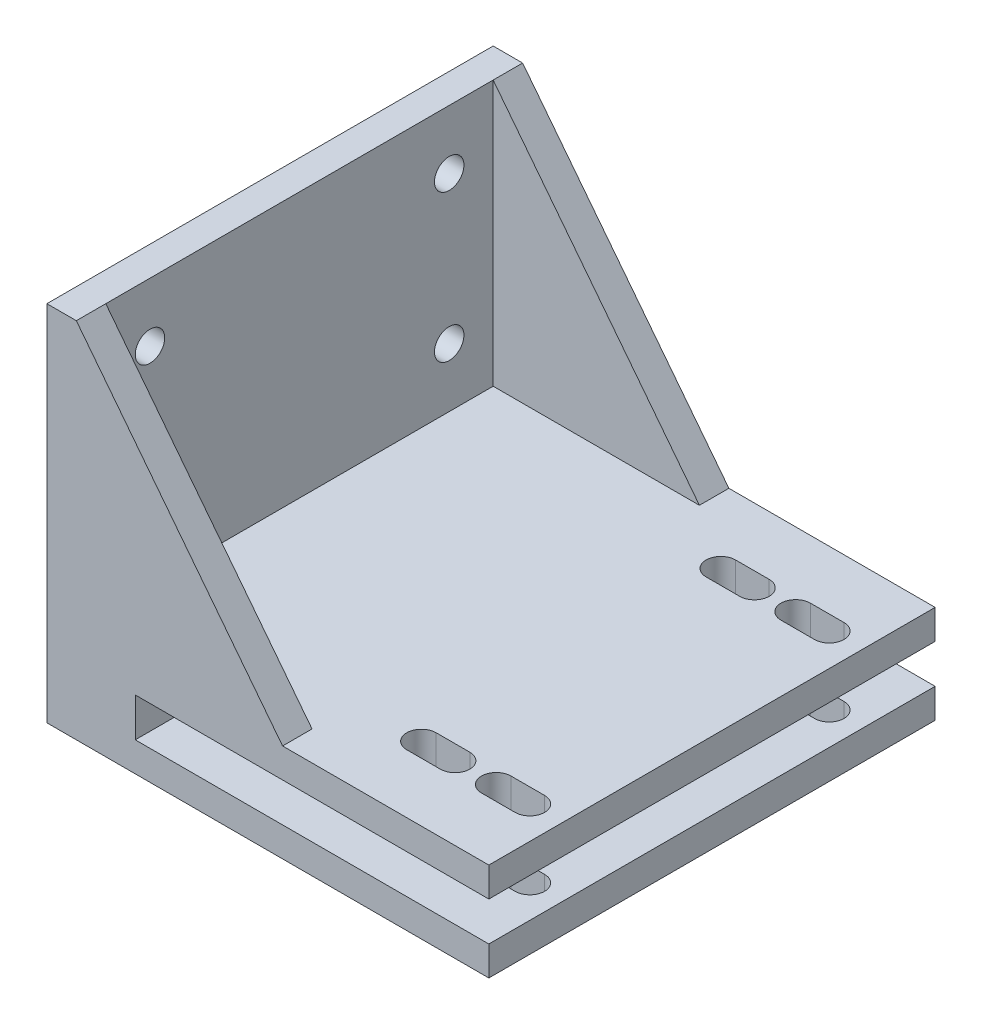
SolidWorks part; units mm, degrees
ref_plane "Front Plane" through (0, 0, 0) normal (0, 0, 1) x (1, 0, 0)
ref_plane "Top Plane" through (0, 0, 0) normal (0, 1, 0) x (1, 0, 0)
ref_plane "Right Plane" through (0, 0, 0) normal (1, 0, 0) x (0, 0, -1)
sketch "Sketch1" plane through (0, 0, 0) normal (0, 1, 0) x (1, 0, 0)
  line L1 (0, 0) -> (75, 0)
  line L2 (0, 0) -> (0, 15)
  line L3 (0, 15) -> (75, 15)
  line L4 (75, 0) -> (75, 15)
  dimension "D1" = 15
  dimension "D2" = 75
extrude "Boss-Extrude1" add sketch "Sketch1" along normal blind 5
sketch "Sketch2" plane through (0, 5, 0) normal (0, 1, 0) x (1, 0, 0)
  line L0 (0, 15) -> (5, 15)
  line L1 (75, 15) -> (0, 15) construction
  line L2 (0, 0) -> (5, 0)
  line L3 (0, 0) -> (75, 0) construction
  line L4 (5, 15) -> (5, 0)
  line L5 (0, 15) -> (0, 0)
extrude "Boss-Extrude2" add sketch "Sketch2" along normal blind 45
sketch "Sketch3" plane through (0, 0, 0) normal (0, -1, 0) x (-1, 0, 0)
  line L0 (0, 7.5) -> (-75, 7.5)
  line L1 (0, 15) -> (0, 0) construction
  line L2 (-75, 0) -> (-75, 15) construction
sketch "Sketch4" plane through (0, 0, 0) normal (-1, 0, 0) x (0, 0, 1)
  line L0 (-7.5, 0) -> (-7.5, 50)
  line L2 (-15, 0) -> (0, 0) construction
  line L3 (-7.5, 0) -> (-7.5, 15)
  line L4 (-7.5, 50) -> (-7.5, 40)
hole_wizard "Ø5.0mm Dowel Hole1" positions "Sketch5" profile "Sketch6" hole size "Ø5.0" standard "ANSI Metric" end condition up to next
sketch "Sketch5" plane through (0, 0, 0) normal (-1, 0, 0) x (0, 0, 1)
  point P0 (-7.5, 40)
  point P3 (-7.5, 15)
  point P6 (0, 0)
  point P7 (-7.5, 40)
sketch "Sketch6" plane through (0, 40, -7.5) normal (0, 1, 0) x (0, 0, 1)
  line L0 (0, 0) -> (0, 5)
  line L1 (0, 5) -> (2.5, 5)
  line L2 (2.5, 5) -> (2.5, 0)
  line L5 (2.5, 0) -> (0, 0)
  line L11 (0, -6.35) -> (0, 107.95) construction
  dimension "Thru Hole Dia." = 5
  dimension "Thru Hole Depth" = 5
hole_wizard "Ø6.0mm Dowel Slot1" positions "Sketch9" profile "Sketch8" size "Ø5.0" standard "ANSI Metric" slot yes end condition up to next
sketch "Sketch9" plane through (0, 0, 0) normal (0, -1, 0) x (-1, 0, 0)
  line L1 (-48.5943, 7.4749) -> (-59.2943, 7.4749) construction
  point P5 (-53.9443, 7.4749)
  point P10 (-66.6443, 7.465)
  dimension "D2" = 10.7
sketch "Sketch8" plane through (53.9443, 0, -7.4749) normal (1, 0, 0) x (0, 0, -1)
  line L0 (0, 0) -> (0, 5)
  line L1 (0, 5) -> (2.5, 5)
  line L2 (2.5, 5) -> (2.5, 0)
  line L5 (2.5, 0) -> (0, 0)
  line L11 (0, -6.35) -> (0, 107.95) construction
  dimension "Thru Hole Dia." = 5
  dimension "Thru Hole Depth" = 5
sketch "Sketch10" plane through (0, 0, 0) normal (0, 0, 1) x (1, 0, 0)
  line L0 (5, 50) -> (40, 5)
  line L1 (5, 5) -> (75, 5) construction
  line L2 (40, 5) -> (75, 5)
  line L3 (75, 5) -> (75, 0)
  line L4 (75, 0) -> (0, 0)
  line L5 (0, 0) -> (0, 50)
  line L6 (0, 50) -> (5, 50)
extrude "Boss-Extrude3" add sketch "Sketch10" along normal blind 5
sketch "Sketch21" plane through (0, 0, -15) normal (0, 0, -1) x (-1, 0, 0)
  line L0 (-75, 5) -> (-5, 5)
  line L1 (-5, 5) -> (-5, 50)
  line L2 (-5, 50) -> (0, 50)
  line L3 (0, 50) -> (0, 0)
  line L4 (0, 0) -> (-75, 0)
  line L5 (-75, 0) -> (-75, 5)
extrude "Boss-Extrude7" add sketch "Sketch21" along normal blind 46.8
sketch "Sketch22" plane through (0, 0, -61.8) normal (0, 0, -1) x (-1, 0, 0)
  line L0 (-75, 5) -> (-40, 5)
  line L1 (-5, 5) -> (-75, 5) construction
  line L3 (-5, 50) -> (0, 50)
  line L4 (0, 50) -> (0, 0)
  line L5 (0, 0) -> (-75, 0)
  line L6 (-75, 0) -> (-75, 5)
  line L7 (-40, 5) -> (-5, 5)
  line L9 (-5, 50) -> (-5, 5)
sketch "Sketch23" plane through (0, 0, 0) normal (0, -1, 0) x (-1, 0, 0)
  line L0 (-53.9443, 4.9749) -> (-53.9443, 9.9749)
  line L1 (-51.0943, 4.9749) -> (-56.7943, 4.9749) construction
  line L2 (-51.0943, 9.9749) -> (-56.7943, 9.9749) construction
  line L3 (-53.9443, 9.9749) -> (-53.9443, 7.4749)
  line L4 (-53.9443, 7.4749) -> (-59.2943, 7.4749)
  line L5 (-66.6443, 9.965) -> (-66.6443, 4.965)
  line L6 (-63.7943, 9.965) -> (-69.4943, 9.965) construction
  line L7 (-63.7943, 4.965) -> (-69.4943, 4.965) construction
  line L8 (-66.6443, 4.965) -> (-66.6443, 7.465)
  line L9 (-66.6443, 7.465) -> (-61.2943, 7.465)
  arc A0 (-56.7943, 9.9749) -> (-56.7943, 4.9749) centre (-56.7943, 7.4749) ccw construction
  arc A1 (-63.7943, 4.965) -> (-63.7943, 9.965) centre (-63.7943, 7.465) ccw construction
sketch "Sketch25" plane through (0, 0, 0) normal (0, -1, 0) x (1, 0, 0)
  line L0 (66.6443, -7.465) -> (66.6443, -58.265)
  line L1 (66.6443, -58.265) -> (66.6443, -70.735)
extrude "Boss-Extrude11" add sketch "Sketch22" along normal up to vertex (8.935 mm away) up to point (66.6443, 0, -70.735)
sketch "Sketch29" plane through (0, 0, 0) normal (0, -1, 0) x (1, 0, 0)
  line L0 (0, -70.735) -> (15, -70.735)
  line L1 (75, -70.735) -> (0, -70.735) construction
  line L2 (15, -70.735) -> (15, 5)
  line L3 (0, 5) -> (75, 5) construction
  line L4 (15, 5) -> (0, 5)
  line L5 (0, 5) -> (0, -70.735)
extrude "Boss-Extrude12" add sketch "Sketch29" along normal blind 11.6
sketch "Sketch30" plane through (15, 0, 0) normal (1, 0, 0) x (0, 0, -1)
  line L0 (70.735, -11.6) -> (70.735, -6.6)
  line L1 (70.735, -11.6) -> (70.735, 0) construction
  line L2 (70.735, -6.6) -> (-5, -6.6)
  line L3 (-5, -11.6) -> (-5, 0) construction
  line L4 (-5, -6.6) -> (-5, -11.6)
  line L5 (-5, -11.6) -> (70.735, -11.6)
extrude "Boss-Extrude13" add sketch "Sketch30" along normal up to surface (60 mm away) up to face at (75, 2.5, -32.8675)
sketch "Sketch31" plane through (0, 0, -70.735) normal (0, 0, -1) x (-1, 0, 0)
  line L0 (-5, 50) -> (-40, 5)
  line L1 (-5, 5) -> (-75, 5) construction
  line L2 (-40, 5) -> (-5, 5)
  line L3 (-5, 5) -> (-5, 50)
extrude "Boss-Extrude14" add sketch "Sketch31" against normal blind 5
hole_wizard "Ø5.0mm Dowel Slot2" positions "Sketch32" profile "Sketch33" size "Ø5.0" standard "ANSI Metric" slot yes end condition through all
sketch "Sketch32" plane through (0, 5, 0) normal (0, 1, 0) x (1, 0, 0)
  line L0 (61.2943, 58.2749) -> (71.9943, 58.2749) construction
  point P0 (66.6443, 58.2749)
  point P5 (53.9443, 58.2749)
  point P9 (0, 0)
  point P10 (0, 0)
  dimension "D1" = 10.7
sketch "Sketch33" plane through (66.6443, 5, -58.2749) normal (1, 0, 0) x (0, 0, 1)
  line L0 (0, 0) -> (0, 16.6)
  line L1 (0, 16.6) -> (2.5, 16.6)
  line L2 (2.5, 16.6) -> (2.5, 0)
  line L5 (2.5, 0) -> (0, 0)
  line L11 (0, -6.35) -> (0, 107.95) construction
  dimension "Thru Hole Dia." = 5
  dimension "Thru Hole Depth" = 16.6
hole_wizard "Ø5.0mm Dowel Slot3" positions "Sketch36" profile "Sketch35" size "Ø5.0" standard "ANSI Metric" slot yes end condition through all
sketch "Sketch36" plane through (0, 0, 0) normal (0, -1, 0) x (-1, 0, 0)
  line L0 (-61.2943, 7.465) -> (-71.9943, 7.465) construction
  point P0 (-66.6443, 7.465)
  point P5 (-53.9443, 7.4749)
  dimension "D1" = 10.7
sketch "Sketch35" plane through (66.6443, 0, -7.465) normal (1, 0, 0) x (0, 0, 1)
  line L0 (0, 0) -> (0, 11.6)
  line L1 (0, 11.6) -> (2.5, 11.6)
  line L2 (2.5, 11.6) -> (2.5, 0)
  line L5 (2.5, 0) -> (0, 0)
  line L11 (0, -6.35) -> (0, 107.95) construction
  dimension "Thru Hole Dia." = 5
  dimension "Thru Hole Depth" = 11.6
sketch "Sketch38" plane through (0, 0, 0) normal (0, -1, 0) x (-1, 0, 0)
  line L0 (-15, 32.8675) -> (-75, 32.8675)
  line L1 (-15, 70.735) -> (-15, -5) construction
  line L2 (-75, -5) -> (-75, 70.735) construction
sketch "Sketch39" plane through (0, 5, 0) normal (0, 1, 0) x (1, 0, 0)
  line L0 (48.5943, 58.2749) -> (5, 58.2749)
  line L1 (5, 0) -> (5, 65.735) construction
  arc A0 (51.0943, 60.7749) -> (51.0943, 55.7749) centre (51.0943, 58.2749) ccw construction
sketch "Sketch40" plane through (5, 0, 0) normal (1, 0, 0) x (0, 0, -1)
  line L0 (58.2749, 5) -> (58.2749, 50)
  line L1 (0, 50) -> (65.735, 50) construction
  line L2 (58.2749, 50) -> (58.2749, 40)
  line L3 (58.2749, 5) -> (58.2749, 15)
hole_wizard "Ø5.0mm Dowel Hole2" positions "Sketch41" profile "Sketch42" hole size "Ø5.0" standard "ANSI Metric" end condition up to next
sketch "Sketch41" plane through (5, 0, 0) normal (1, 0, 0) x (0, 0, -1)
  point P0 (58.2749, 40)
  point P3 (58.2749, 15)
sketch "Sketch42" plane through (5, 40, -58.2749) normal (0, 1, 0) x (0, 0, -1)
  line L0 (0, 0) -> (0, 5)
  line L1 (0, 5) -> (2.5, 5)
  line L2 (2.5, 5) -> (2.5, 0)
  line L5 (2.5, 0) -> (0, 0)
  line L11 (0, -6.35) -> (0, 107.95) construction
  dimension "Thru Hole Dia." = 5
  dimension "Thru Hole Depth" = 5
